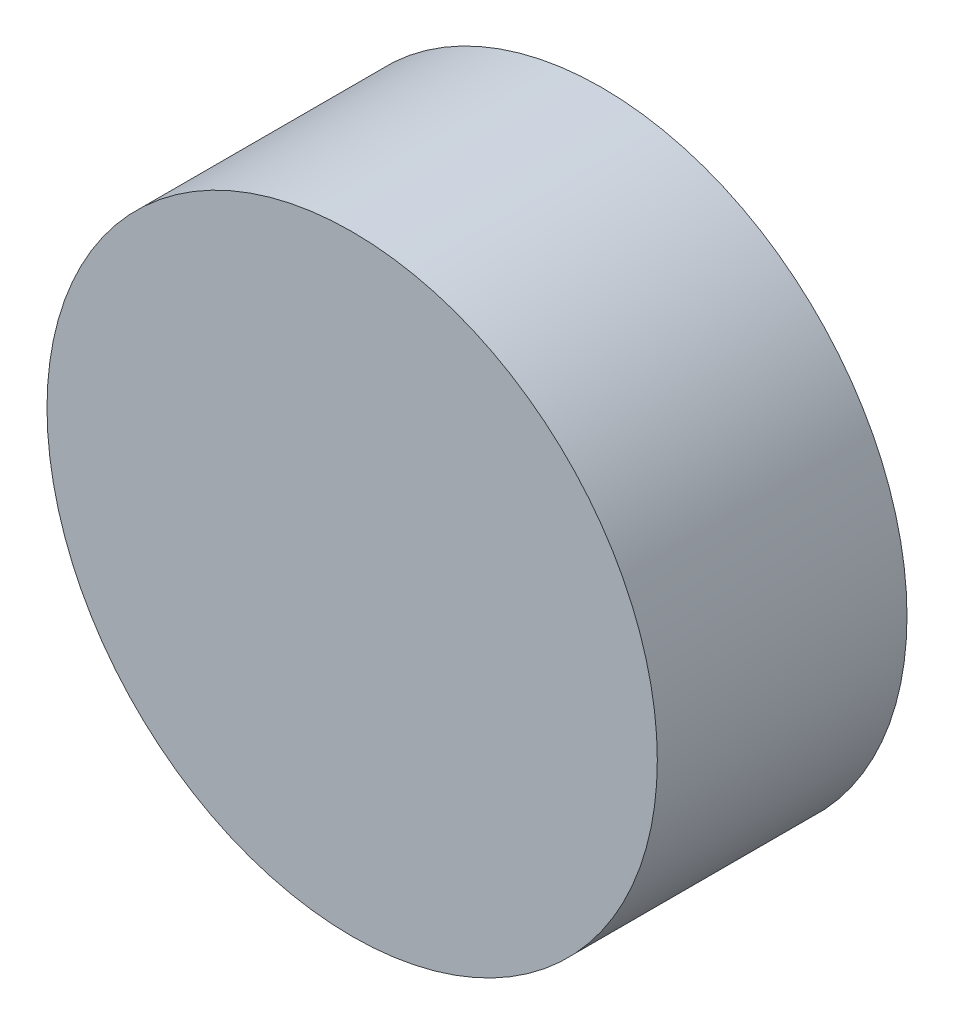
SolidWorks part; units mm, degrees
material "PE Low Density Film"
ref_plane "Front Plane" through (0, 0, 0) normal (0, 0, 1) x (1, 0, 0)
ref_plane "Top Plane" through (0, 0, 0) normal (0, 1, 0) x (1, 0, 0)
ref_plane "Right Plane" through (0, 0, 0) normal (1, 0, 0) x (0, 0, -1)
ref_plane "Plane1" through (0, 0, 0) normal (0, -1, 0) x (-1, 0, 0)
sketch "Sketch3" plane through (0, 0, 0) normal (0, -1, 0) x (-1, 0, 0)
  line L0 (0, 0) -> (0, -44.7518) construction
  line L1 (31.75, -25.4) -> (31.75, 0) construction
  line L2 (31.75, -25.4) -> (31.75, 0)
  line L3 (34.925, -25.4) -> (34.925, 0)
  line L4 (34.925, -25.4) -> (34.925, -28.575)
  line L5 (34.925, -28.575) -> (0, -28.575)
  line L6 (-31.75, -25.4) -> (31.75, -25.4) construction
  line L7 (0, -25.4) -> (31.75, -25.4)
  line L8 (0, -28.575) -> (0, -25.4)
  line L9 (34.925, 0) -> (31.75, 0)
  dimension "D2" = 3.175
  dimension "D1" = 3.175
revolve "Revolve1" add sketch "Sketch3" angle 360 about L0
